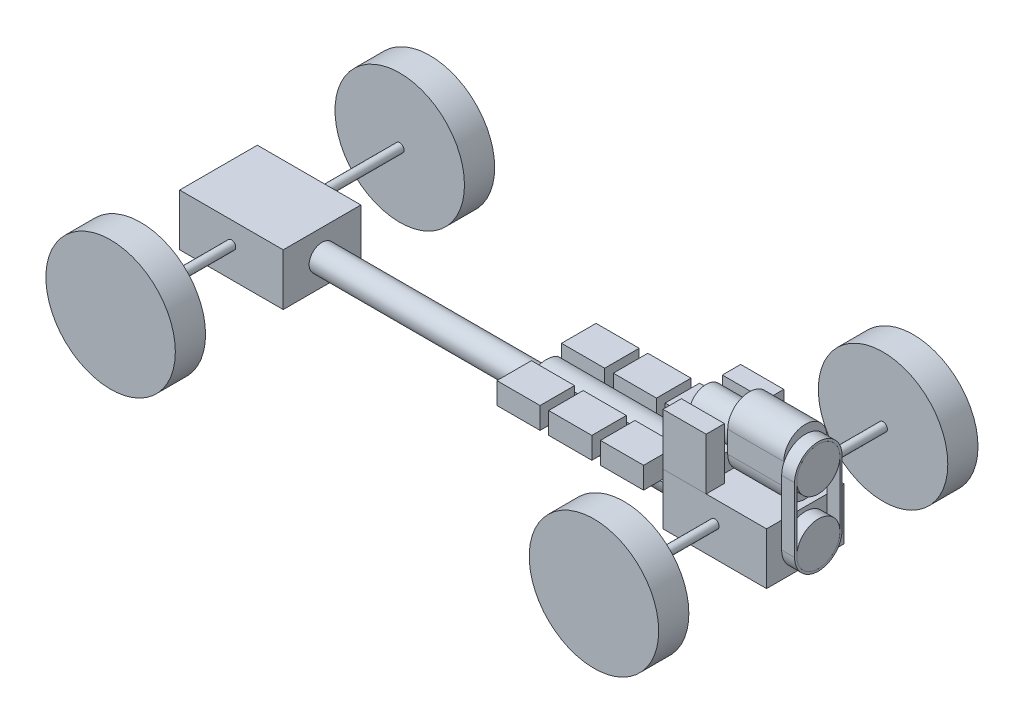
SolidWorks part; units mm, degrees
ref_plane "Front Plane" through (0, 0, 0) normal (0, 0, 1) x (1, 0, 0)
ref_plane "Top Plane" through (0, 0, 0) normal (0, 1, 0) x (1, 0, 0)
ref_plane "Right Plane" through (0, 0, 0) normal (1, 0, 0) x (0, 0, -1)
sketch "Sketch1" plane through (0, 0, 0) normal (0, 1, 0) x (1, 0, 0)
  line L1 (-1422.4, -850.9) -> (1422.4, -850.9) construction
  line L2 (-1422.4, -850.9) -> (-1422.4, 850.9) construction
  line L3 (-1422.4, 850.9) -> (1422.4, 850.9) construction
  line L4 (1422.4, -850.9) -> (1422.4, 850.9) construction
  line L5 (-1422.4, -850.9) -> (1422.4, 850.9) construction
  line L6 (-1422.4, 850.9) -> (1422.4, -850.9) construction
  line L7 (-1727.2, -228.6) -> (-1117.6, -228.6)
  line L8 (-1727.2, -228.6) -> (-1727.2, 228.6)
  line L9 (-1727.2, 228.6) -> (-1117.6, 228.6)
  line L10 (-1117.6, -228.6) -> (-1117.6, 228.6)
  line L11 (-1727.2, -228.6) -> (-1117.6, 228.6) construction
  line L12 (-1727.2, 228.6) -> (-1117.6, -228.6) construction
  line L13 (1117.6, -228.6) -> (1727.2, -228.6)
  line L14 (1117.6, -228.6) -> (1117.6, 228.6)
  line L15 (1117.6, 228.6) -> (1727.2, 228.6)
  line L16 (1727.2, -228.6) -> (1727.2, 228.6)
  line L17 (1117.6, -228.6) -> (1727.2, 228.6) construction
  line L18 (1117.6, 228.6) -> (1727.2, -228.6) construction
  point P0 (0, 0)
  point P5 (-1422.4, 0)
  point P11 (1422.4, 0)
  dimension "D1" = 2844.8
  dimension "D2" = 1701.8
  dimension "D3" = 609.6
  dimension "D4" = 457.2
sketch "Sketch2" plane through (0, 0, 0) normal (0, 0, 1) x (1, 0, 0)
  line L0 (-1422.4, 0) -> (1422.4, 0) construction
  line L1 (-1422.4, 0) -> (1422.4, 0) construction
  line L2 (-1422.4, 0) -> (-1422.4, 381) construction
  line L3 (-1422.4, 381) -> (1422.4, 381) construction
  line L4 (1422.4, 381) -> (1422.4, 0) construction
  circle A0 centre (-1422.4, 381) radius 381
  circle A1 centre (1422.4, 381) radius 381
  point P6 (1422.4, 241.4805)
  point P9 (0, 0)
  point P10 (0, 0)
  dimension "D1" = 381
ref_plane "Plane1" through (0, 0, 850.9) normal (0, 0, 1) x (1, 0, 0)
ref_plane "Plane2" through (0, 0, -850.9) normal (0, 0, 1) x (1, 0, 0)
sketch "Sketch3" plane through (0, 0, 850.9) normal (0, 0, 1) x (1, 0, 0)
  circle A0 centre (1422.4, 381) radius 381 construction
  circle A1 centre (-1422.4, 381) radius 381 construction
  circle A2 centre (1422.4, 381) radius 381
  circle A3 centre (-1422.4, 381) radius 381
sketch "Sketch4" plane through (0, 0, -850.9) normal (0, 0, 1) x (1, 0, 0)
  circle A0 centre (1422.4, 381) radius 381 construction
  circle A1 centre (-1422.4, 381) radius 381 construction
  circle A2 centre (1422.4, 381) radius 381
  circle A3 centre (-1422.4, 381) radius 381
extrude "Boss-Extrude1" add sketch "Sketch4" along normal mid plane 177.8
extrude "Boss-Extrude2" add sketch "Sketch3" along normal mid plane 177.8 separate body contours A3 | A2
extrude "Boss-Extrude3" add sketch "Sketch1" along normal blind 304.8 from offset 203.2 separate body contours L13 L16 L15 L14 | L7 L10 L9 L8 region at (-1422.4, 0, 0) region at (1422.4, 0, 0)
sketch "Sketch5" plane through (1117.6, 0, 0) normal (-1, 0, 0) x (0, 0, 1)
  line L0 (0, 508) -> (0, 203.2) construction
  line L1 (0, 355.6) -> (0, 279.4) construction
  line L2 (0, 355.6) -> (-65.9911, 393.7) construction
  line L3 (0, 355.6) -> (65.9911, 393.7) construction
  line L4 (-228.6, 203.2) -> (228.6, 203.2)
  line L5 (228.6, 203.2) -> (228.6, 508)
  line L6 (228.6, 508) -> (-228.6, 508)
  line L7 (-228.6, 508) -> (-228.6, 203.2)
  line L8 (-228.6, 203.2) -> (228.6, 203.2) construction
  line L9 (228.6, 203.2) -> (228.6, 508) construction
  line L10 (228.6, 508) -> (-228.6, 508) construction
  line L11 (-228.6, 508) -> (-228.6, 203.2) construction
  line L12 (-228.6, 203.2) -> (228.6, 203.2)
  line L13 (228.6, 203.2) -> (228.6, 508)
  line L14 (228.6, 508) -> (-228.6, 508)
  line L15 (-228.6, 508) -> (-228.6, 203.2)
  line L16 (-228.6, 203.2) -> (228.6, 203.2) construction
  line L17 (228.6, 203.2) -> (228.6, 508) construction
  line L18 (228.6, 508) -> (-228.6, 508) construction
  line L19 (-228.6, 508) -> (-228.6, 203.2) construction
  line L20 (-65.9911, 393.7) -> (-65.9911, 478.7311)
  line L21 (65.9911, 393.7) -> (65.9911, 478.7311)
  line L22 (65.9911, 393.7) -> (139.6302, 351.1845)
  line L23 (0, 279.4) -> (73.6391, 236.8845)
  line L24 (0, 279.4) -> (-73.6391, 236.8845)
  line L25 (-65.9911, 393.7) -> (-139.6302, 351.1845)
  circle A0 centre (0, 355.6) radius 139.7 construction
  circle A1 centre (0, 355.6) radius 76.2
  arc A2 (65.9911, 478.7311) -> (-65.9911, 478.7311) centre (0, 355.6) ccw
  arc A3 (73.6391, 236.8845) -> (139.6302, 351.1845) centre (0, 355.6) ccw
  arc A4 (-139.6302, 351.1845) -> (-73.6391, 236.8845) centre (0, 355.6) ccw
  point P19 (0, 355.6)
  point P32 (0, 355.6)
  dimension "D3" = 279.4
  dimension "D4" = 152.4
  dimension "D5" = 76.2
  dimension "D1" = 0
  dimension "D2" = 0
extrude "Boss-Extrude4" add sketch "Sketch5" along normal blind 914.4 separate body contours L21 A2 L20 A1 | L23 A3 L22 A1 | L25 A4 L24 A1 | A1 region at (1117.6, 306.067, -85.7936) region at (1117.6, 454.666, 0) region at (1117.6, 355.6, 0) region at (1117.6, 306.067, 85.7936)
extrude "Boss-Extrude5" add sketch "Sketch5<3>" along normal up to surface (2235.2 mm away) separate body contours A1 up to face at (-1117.6, 355.6, 0)
sketch "Sketch5<3>" plane through (1117.6, 0, 0) normal (-1, 0, 0) x (0, 0, 1) same geometry as "Sketch5"
sketch "Sketch6" plane through (1727.2, 0, 0) normal (1, 0, 0) x (0, 0, -1)
  line L0 (0, 736.6) -> (0, 355.6) construction
  line L1 (-127, 355.6) -> (-127, 736.6)
  line L2 (127, 736.6) -> (127, 355.6)
  line L3 (139.7, 736.6) -> (139.7, 355.6)
  line L4 (-139.7, 355.6) -> (-139.7, 736.6)
  circle A0 centre (0, 355.6) radius 127
  circle A1 centre (0, 736.6) radius 127
  arc A2 (-127, 736.6) -> (127, 736.6) centre (0, 736.6) cw
  arc A3 (127, 355.6) -> (-127, 355.6) centre (0, 355.6) cw
  arc A4 (-139.7, 736.6) -> (139.7, 736.6) centre (0, 736.6) cw
  arc A5 (139.7, 355.6) -> (-139.7, 355.6) centre (0, 355.6) cw
  dimension "D1" = 254
  dimension "D2" = 381
  dimension "D3" = 381
  dimension "D4" = 12.7
extrude "Boss-Extrude6" add sketch "Sketch6" along normal blind 76.2 separate body contours A1 | A0
sketch "Sketch8" plane through (1727.2, 0, 0) normal (-1, 0, 0) x (0, 0, 1)
  line L0 (0, 673.1) -> (0, 800.1) construction
  line L1 (-127, 673.1) -> (-127, 800.1)
  line L2 (127, 673.1) -> (127, 800.1)
  arc A0 (-127, 673.1) -> (127, 673.1) centre (0, 673.1) ccw
  circle A1 centre (0, 736.6) radius 127
  circle A2 centre (0, 736.6) radius 127 construction
  arc A3 (127, 800.1) -> (-127, 800.1) centre (0, 800.1) ccw
  point P5 (0, 736.6)
  dimension "D2" = 127
  dimension "D3" = 127
  dimension "D1" = 0
extrude "Boss-Extrude8" add sketch "Sketch8" along normal blind 330.2 separate body contours A3 L1 A0 L2
sketch "Sketch9" plane through (1397, 0, 0) normal (-1, 0, 0) x (0, 0, 1)
  line L0 (0, 800.1) -> (0, 673.1) construction
  line L2 (127, 673.1) -> (127, 800.1)
  line L3 (-127, 800.1) -> (-127, 673.1)
  line L4 (127, 673.1) -> (127, 800.1) construction
  line L5 (-127, 800.1) -> (-127, 673.1) construction
  line L6 (255.5028, 736.6) -> (255.5028, 737.5355) construction
  circle A0 centre (0, 736.6) radius 101.6
  arc A2 (127, 800.1) -> (-127, 800.1) centre (0, 800.1) ccw
  arc A3 (-127, 673.1) -> (127, 673.1) centre (0, 673.1) ccw
  arc A4 (127, 800.1) -> (-127, 800.1) centre (0, 800.1) ccw construction
  arc A5 (-127, 673.1) -> (127, 673.1) centre (0, 673.1) ccw construction
  dimension "D2" = 203.2
  dimension "D1" = 0
extrude "Boss-Extrude9" add sketch "Sketch9" along normal blind 254 separate body
extrude "Boss-Extrude10" add sketch "Sketch6<3>" along normal blind 76.2 separate body contours L4 A4 L3 A5 | L1 A2 L2 A3
sketch "Sketch6<3>" plane through (1727.2, 0, 0) normal (1, 0, 0) x (0, 0, -1) same geometry as "Sketch6"
ref_plane "Plane3" through (0, 406.4, 0) normal (0, 1, 0) x (1, 0, 0)
sketch "Sketch11" plane through (0, 406.4, 0) normal (0, 1, 0) x (1, 0, 0)
  line L0 (508, -88.6601) -> (508, -291.8601)
  line L1 (508, -88.6601) -> (762, -88.6601)
  line L2 (762, -88.6601) -> (762, -291.8601)
  line L3 (203.2, -88.6601) -> (457.2, -88.6601)
  line L4 (203.2, 0) -> (1117.6, 0) construction
  line L5 (203.2, 65.9911) -> (203.2, -65.9911) construction
  line L6 (1117.6, 228.6) -> (1117.6, -228.6) construction
  line L7 (203.2, -88.6601) -> (203.2, -291.8601)
  line L12 (203.2, -291.8601) -> (457.2, -291.8601)
  line L13 (457.2, -88.6601) -> (457.2, -291.8601)
  line L14 (508, -291.8601) -> (762, -291.8601)
  line L15 (812.8, -88.6601) -> (812.8, -291.8601)
  line L16 (812.8, -88.6601) -> (1066.8, -88.6601)
  line L17 (1066.8, -88.6601) -> (1066.8, -291.8601)
  line L18 (812.8, -291.8601) -> (1066.8, -291.8601)
  line L19 (812.8, 88.6601) -> (1066.8, 88.6601)
  line L20 (1066.8, 88.6601) -> (1066.8, 291.8601)
  line L21 (812.8, 291.8601) -> (1066.8, 291.8601)
  line L22 (812.8, 88.6601) -> (812.8, 291.8601)
  line L23 (508, 88.6601) -> (762, 88.6601)
  line L24 (762, 88.6601) -> (762, 291.8601)
  line L25 (508, 291.8601) -> (762, 291.8601)
  line L26 (508, 88.6601) -> (508, 291.8601)
  line L27 (203.2, 291.8601) -> (457.2, 291.8601)
  line L28 (457.2, 88.6601) -> (457.2, 291.8601)
  line L29 (203.2, 88.6601) -> (457.2, 88.6601)
  line L30 (203.2, 88.6601) -> (203.2, 291.8601)
  dimension "D1" = 203.2
  dimension "D2" = 254
  dimension "D3" = 3
extrude "Boss-Extrude11" add sketch "Sketch11" along normal blind 127 separate body
sketch "Sketch12" plane through (0, 508, 0) normal (0, 1, 0) x (1, 0, 0)
  line L0 (1117.6, 228.6) -> (1371.6, 228.6)
  line L1 (1117.6, 228.6) -> (1727.2, 228.6) construction
  line L2 (1371.6, 228.6) -> (1371.6, 120.65)
  line L3 (1371.6, 120.65) -> (1117.6, 120.65)
  line L4 (1117.6, 120.65) -> (1117.6, 228.6)
  line L5 (1397, 0) -> (1117.6, 0) construction
  line L7 (1371.6, -120.65) -> (1117.6, -120.65)
  line L8 (1371.6, -228.6) -> (1371.6, -120.65)
  line L9 (1117.6, -228.6) -> (1371.6, -228.6)
  line L10 (1117.6, -120.65) -> (1117.6, -228.6)
  line L11 (1320.8, 120.65) -> (1320.8, -120.65)
  line L12 (1143, 120.65) -> (1143, -120.65)
  line L13 (1143, 120.65) -> (1320.8, 120.65)
  line L14 (1143, -120.65) -> (1320.8, -120.65)
  point P20 (0, 0)
  line M12 (1117.6, -228.6) -> (1727.2, -228.6)
  line M14 (1727.2, 228.6) -> (1117.6, 228.6)
  line M15 (1117.6, 228.6) -> (1117.6, -228.6)
  dimension "D1" = 254
  dimension "D2" = 107.95
  dimension "D3" = 177.8
  dimension "D4" = 50.8
extrude "Boss-Extrude12" add sketch "Sketch12" along normal blind 304.8 separate body contours L3 L2 M14 M15 | L8 L7 M12 M15 region at (1244.6, 508, -174.625) region at (1244.6, 508, 174.625)
extrude "Boss-Extrude13" add sketch "Sketch12<3>" along normal blind 101.6 contours L11 L5 L12 L7 | L5 L11 L3 L12 region at (1231.9, 508, -60.325) region at (1231.9, 508, 60.325)
sketch "Sketch12<3>" plane through (0, 508, 0) normal (0, 1, 0) x (1, 0, 0) same geometry as "Sketch12"
sketch "Sketch13" plane through (0, 0, -762) normal (0, 0, 1) x (1, 0, 0)
  circle A0 centre (-1422.4, 381) radius 25.4
  circle A1 centre (1422.4, 381) radius 25.4
  dimension "D1" = 50.8
extrude "Boss-Extrude15" add sketch "Sketch13" along normal up to surface (1524 mm away) up to face at (-1041.4, 381, 762)
